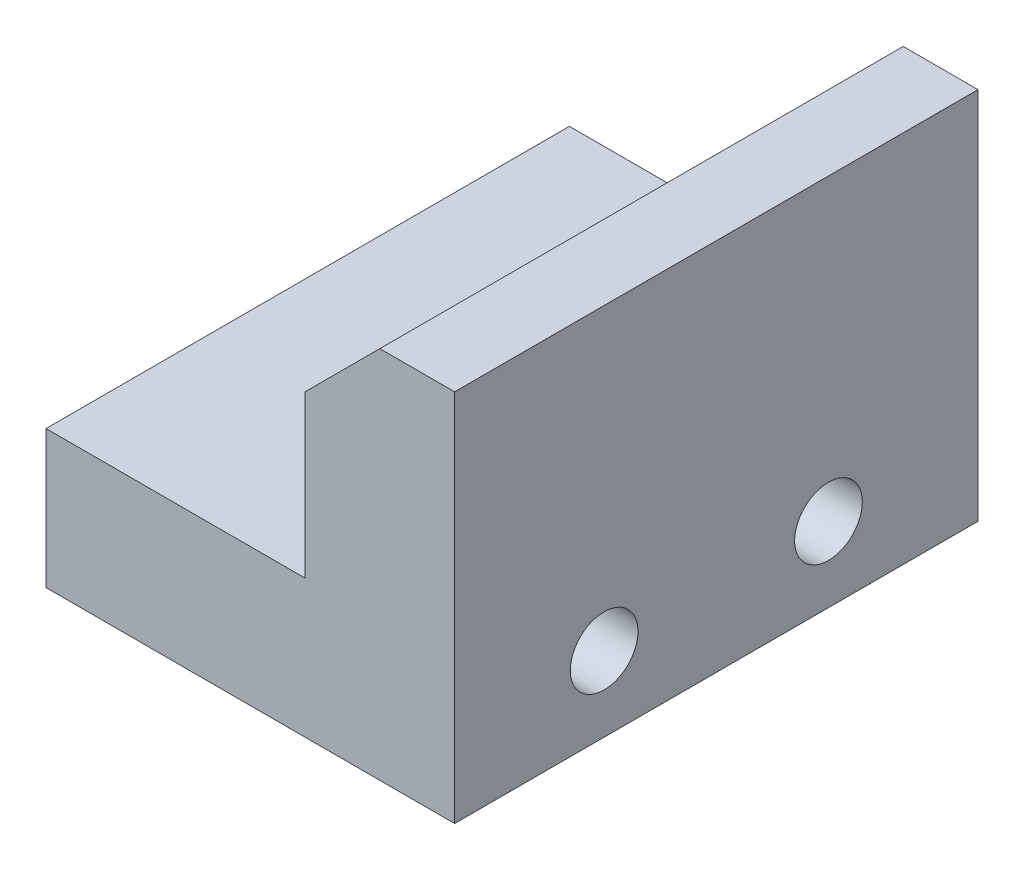
SolidWorks part; units mm, degrees
material "PETG"
ref_plane "Front Plane" through (0, 0, 0) normal (0, 0, 1) x (1, 0, 0)
ref_plane "Top Plane" through (0, 0, 0) normal (0, 1, 0) x (1, 0, 0)
ref_plane "Right Plane" through (0, 0, 0) normal (1, 0, 0) x (0, 0, -1)
sketch "Sketch1" plane through (0, 0, 0) normal (0, 0, 1) x (1, 0, 0)
  line L0 (69.4, 63.5) -> (44, 38.1)
  line L1 (0, -12.7) -> (69.4, -12.7)
  line L2 (0, -12.7) -> (0, 12.7)
  line L3 (0, 12.7) -> (44, 12.7)
  line L5 (44, 63.5) -> (69.4, 63.5)
  line L6 (44, 63.5) -> (44, 12.7)
  line L8 (69.4, 63.5) -> (69.4, -12.7)
  line L9 (56.7, 50.8) -> (69.4, 50.8)
  line L10 (0, 10.7) -> (44, 10.7)
  line L11 (44, 10.7) -> (44, 12.7)
  dimension "D1" = 25.4
  dimension "D2" = 69.4
  dimension "D3" = 25.4
  dimension "D4" = 50.8
  dimension "D5" = 25.4
  dimension "D6" = 12.7
  dimension "D7" = 2
extrude "Boss-Extrude1" add sketch "Sketch1" along normal mid plane 88.9 contours L8 L0 L6 L3 L2 L1 region at (43.0207, 10.1258, 0)
sketch "Sketch2" plane through (69.4, 0, 0) normal (1, 0, 0) x (0, 0, -1)
  line L0 (-19.05, 0) -> (0, 0) construction
  line L1 (0, 0) -> (19.05, 0) construction
  line L2 (-44.45, 50.8) -> (-44.45, -12.7) construction
  circle A0 centre (-19.05, 0) radius 3.25
  circle A1 centre (19.05, 0) radius 3.25
  dimension "D1" = 6.5
  dimension "D2" = 25.4
extrude "Cut-Extrude1" cut sketch "Sketch2" against normal through all
sketch "Sketch3" plane through (69.4, 0, 0) normal (1, 0, 0) x (0, 0, -1)
  circle A0 centre (-19.05, 0) radius 5.75
  circle A1 centre (19.05, 0) radius 5.75
  dimension "D1" = 11.5
extrude "Cut-Extrude2" cut sketch "Sketch3" against normal offset from surface (59.4 mm away) 10 up to face at (0, 0, 15.8)
equation "\"D2@Sketch1\"  = 44mm + 1in"
